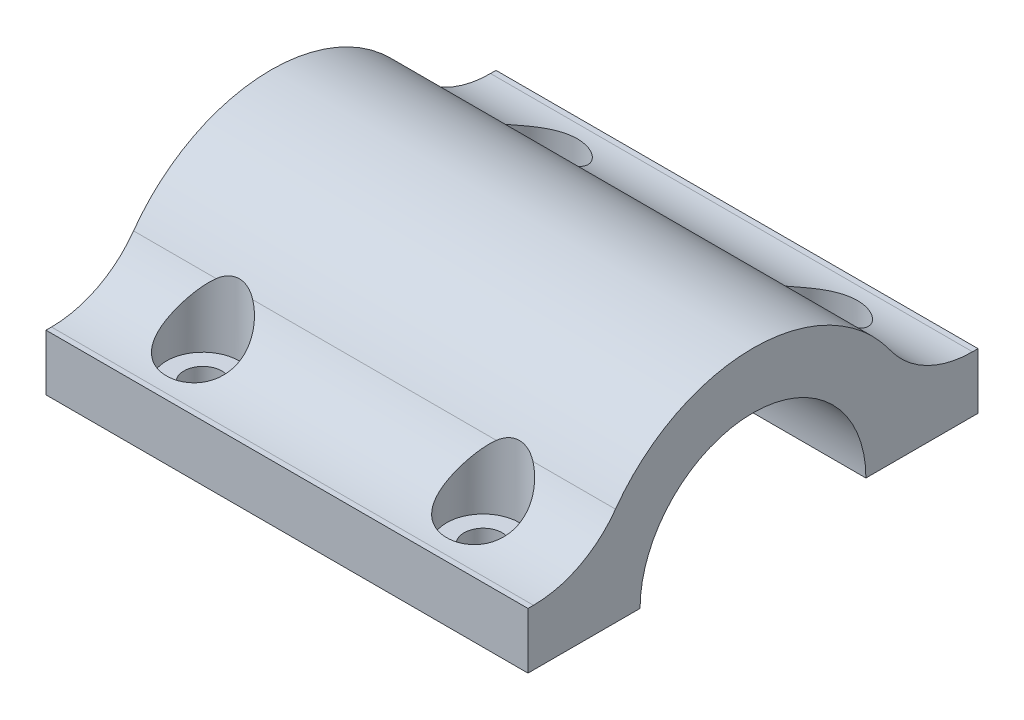
SolidWorks part; units mm, degrees
material "ABS"
ref_plane "Front Plane" through (0, 0, 0) normal (0, 0, 1) x (1, 0, 0)
ref_plane "Top Plane" through (0, 0, 0) normal (0, 1, 0) x (1, 0, 0)
ref_plane "Right Plane" through (0, 0, 0) normal (1, 0, 0) x (0, 0, -1)
sketch "Sketch1" plane through (0, 0, 0) normal (1, 0, 0) x (0, 0, -1)
  line L0 (-10.075, 0) -> (-20.075, 0)
  line L1 (-20.075, 0) -> (-20.075, 5)
  line L2 (-20.075, 5) -> (-14.2217, 5)
  line L3 (14.2217, 5) -> (20.075, 5)
  line L4 (20.075, 5) -> (20.075, 0)
  line L5 (20.075, 0) -> (10.075, 0)
  arc A0 (10.075, 0) -> (-10.075, 0) centre (0, 0) ccw
  arc A2 (-14.2217, 5) -> (14.2217, 5) centre (0, 0) cw
  dimension "D1" = 5
  dimension "D2" = 20.15
  dimension "D3" = 10
  dimension "D4" = 5
  dimension "D5" = 5.8533
extrude "Boss-Extrude1" add sketch "Sketch1" along normal mid plane 43
sketch "Sketch3" plane through (0, 0, 0) normal (0, -1, 0) x (1, 0, 0)
  line L0 (-21.5, 15.075) -> (-12.5, 15.075) construction
  line L1 (-21.5, 20.075) -> (-21.5, 10.075) construction
  line L2 (-12.5, 15.075) -> (0, 15.075) construction
  line L3 (0, 15.075) -> (12.5, 15.075) construction
  line L4 (12.5, 15.075) -> (21.5, 15.075) construction
  line L5 (21.5, 20.075) -> (21.5, 10.075) construction
  point P10 (-12.5, 15.075)
  point P11 (12.5, 15.075)
  dimension "D1" = 25
hole_wizard "CBORE for M3 SHCS1" positions "Sketch3" profile "Sketch4" counterbore size "M3" standard "ANSI Metric" end condition through all
sketch "Sketch4" plane through (12.5, 0, 15.075) normal (1, 0, 0) x (0, 0, -1)
  line L0 (0, 0) -> (0, 15.075)
  line L1 (0, 15.075) -> (3.25, 15.075)
  line L3 (3.25, 15.075) -> (3.25, 3)
  line L4 (3.25, 3) -> (1.7, 3)
  line L5 (1.7, 3) -> (1.7, 0)
  line L7 (1.7, 0) -> (0, 0)
  line L11 (0, -6.35) -> (0, 107.95) construction
  dimension "Thru Hole Dia." = 6.5
  dimension "Thru Hole Depth" = 15.075
  dimension "C'Bore Dia." = 3.4
  dimension "C'Bore Depth" = 3
mirror "Mirror1" about plane through (0, 0, 0) normal (0, 0, 1) of "CBORE for M3 SHCS1"
fillet "Fillet1" radius 9 6 edges at (-18.568, 5, -14.2217) (-18.568, 5, 14.2217) (18.568, 5, -14.2217) (0, 5, -14.2217) (18.568, 5, 14.2217) (0, 5, 14.2217)
equation "\"spar_diameter\"= 20mm"
equation "\"D2@Sketch1\"=\"spar_diameter\"+0.15"
